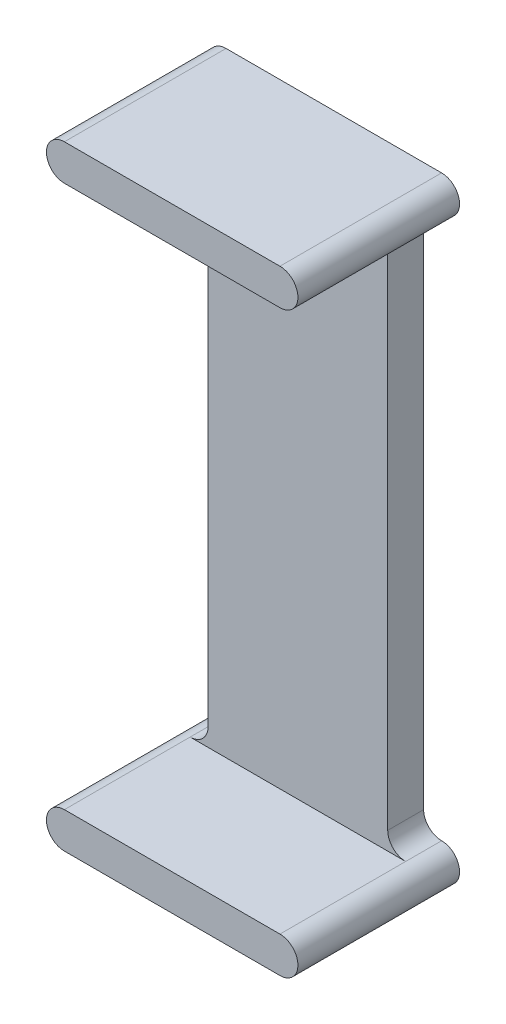
SolidWorks part; units mm, degrees
ref_plane "Front Plane" through (0, 0, 0) normal (0, 0, 1) x (1, 0, 0)
ref_plane "Top Plane" through (0, 0, 0) normal (0, 1, 0) x (1, 0, 0)
ref_plane "Right Plane" through (0, 0, 0) normal (1, 0, 0) x (0, 0, -1)
sketch "Sketch1" plane through (0, 0, 0) normal (0, 0, 1) x (1, 0, 0)
  line L0 (-5, 0) -> (5, 0) construction
  line L1 (0, 0) -> (0, 16) construction
  line L4 (-5, 15.1) -> (-5, 0.9)
  line L6 (5, 15.1) -> (5, 0.9)
  line L7 (-5, 12) -> (5, -12) construction
  line L8 (-5, -12) -> (5, 12) construction
  line L12 (-5, -1.1) -> (-5, -15.1)
  line L13 (5, -1.1) -> (5, -15.1)
  line L14 (-5, 8) -> (5, 8) construction
  line L15 (6, 15.1) -> (5, 15.1)
  line L16 (6, 17.1) -> (5, 17.1)
  line L17 (-6, 15.1) -> (-5, 15.1)
  line L18 (-6, 17.1) -> (-5, 17.1)
  line L19 (6, -17.1) -> (5, -17.1)
  line L20 (6, -15.1) -> (5, -15.1)
  line L21 (-6, -15.1) -> (-5, -15.1)
  line L22 (-6, -17.1) -> (5, -17.1)
  line L23 (-5, 17.1) -> (5, 17.1)
  line L24 (6, 16.1) -> (-6, 16.1) construction
  line L25 (6, -16.1) -> (-6, -16.1) construction
  line L26 (5, 0.9) -> (5, -1.1)
  line L27 (-5, 0.9) -> (-5, -1.1)
  arc A2 (6, 15.1) -> (6, 17.1) centre (6, 16.1) ccw
  arc A3 (-6, 15.1) -> (-6, 17.1) centre (-6, 16.1) cw
  arc A4 (6, -15.1) -> (6, -17.1) centre (6, -16.1) cw
  arc A5 (-6, -15.1) -> (-6, -17.1) centre (-6, -16.1) ccw
  point P3 (0, 0)
  point P4 (0, 0)
  point P8 (0, 0)
  point P9 (0, 0)
  point P24 (0, 8)
  dimension "D3" = 10
  dimension "D4" = 32.2
extrude "Boss-Extrude3" add sketch "Sketch1" along normal blind 2
sketch "Sketch3" plane through (0, 0, 2) normal (0, 0, 1) x (1, 0, 0)
  line L0 (-6, 15.1) -> (-5, 15.1) construction
  line L1 (5, 15.1) -> (6, 15.1) construction
  line L4 (6, 17.1) -> (-6, 17.1) construction
  line L5 (-6, 15.1) -> (-5, 15.1)
  line L6 (5, 15.1) -> (6, 15.1)
  line L7 (6, 17.1) -> (-6, 17.1)
  line L8 (-5, 15.1) -> (5, 15.1)
  line L9 (-5, 0) -> (5, 0) construction
  line L10 (-5, 15.1) -> (-5, -15.1) construction
  line L11 (5, -15.1) -> (5, 15.1) construction
  line L12 (-6, -15.1) -> (-5, -15.1)
  line L13 (6, -17.1) -> (-6, -17.1)
  line L14 (5, -15.1) -> (6, -15.1)
  line L15 (-5, -15.1) -> (5, -15.1)
  arc A7 (-6, 17.1) -> (-6, 15.1) centre (-6, 16.1) ccw construction
  arc A8 (6, 15.1) -> (6, 17.1) centre (6, 16.1) ccw construction
  arc A9 (-6, 17.1) -> (-6, 15.1) centre (-6, 16.1) ccw
  arc A10 (6, 15.1) -> (6, 17.1) centre (6, 16.1) ccw
  arc A11 (-6, -17.1) -> (-6, -15.1) centre (-6, -16.1) cw
  arc A12 (6, -15.1) -> (6, -17.1) centre (6, -16.1) cw
extrude "Boss-Extrude4" add sketch "Sketch3" along normal blind 7
fillet "Fillet2" radius 1 4 edges at (-5, 15.1, 1) (-5, -15.1, 1) (5, 15.1, 1) (5, -15.1, 1)
